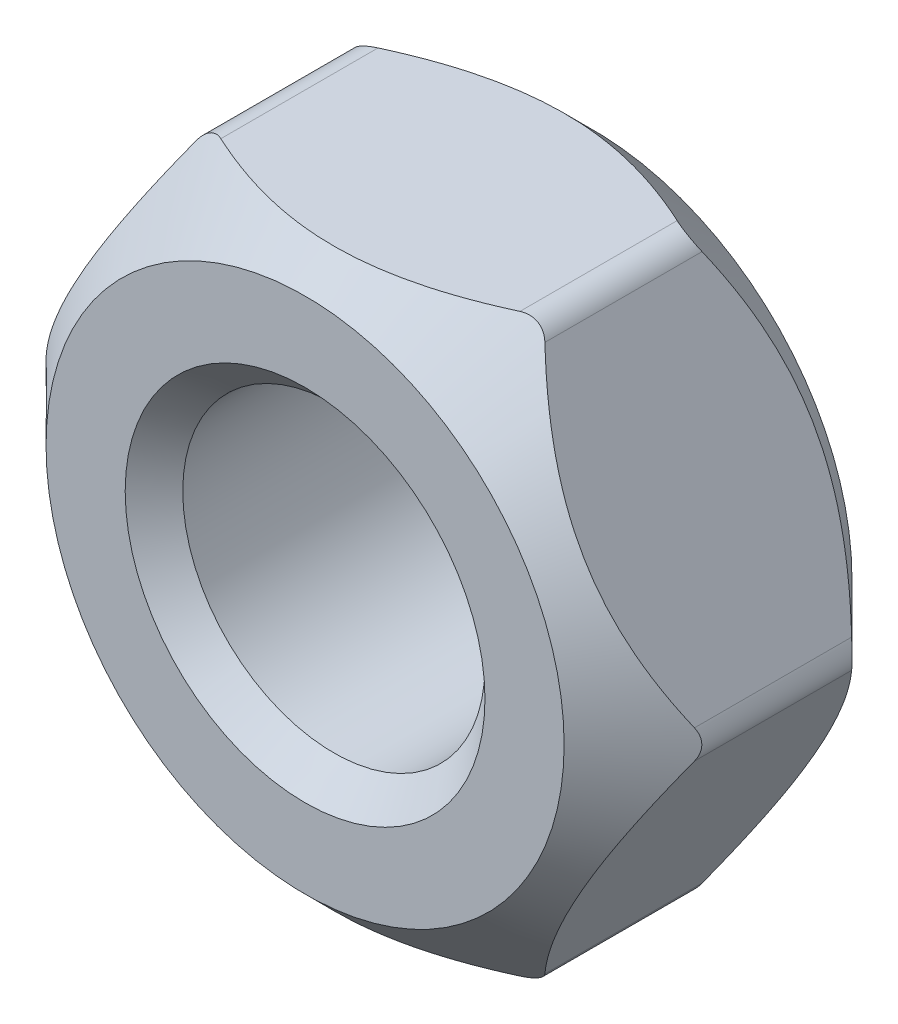
SolidWorks part; units mm, degrees
ref_plane "Front Plane" through (0, 0, 0) normal (0, 0, 1) x (1, 0, 0)
ref_plane "Top Plane" through (0, 0, 0) normal (0, 1, 0) x (1, 0, 0)
ref_plane "Right Plane" through (0, 0, 0) normal (1, 0, 0) x (0, 0, -1)
sketch "Sketch1" plane through (0, 0, 0) normal (0, 0, 1) x (1, 0, 0)
  line L1 (1.7321, 3) -> (-1.7321, 3)
  line L2 (-1.7321, 3) -> (-3.4641, 0)
  line L3 (-3.4641, 0) -> (-1.7321, -3)
  line L4 (-1.7321, -3) -> (1.7321, -3)
  line L5 (1.7321, -3) -> (3.4641, 0)
  line L6 (3.4641, 0) -> (1.7321, 3)
  circle A0 centre (0, 0) radius 1.575
  circle A1 centre (0, 0) radius 3 construction
  point P3 (2.103, 3.5722)
  dimension "D3" = 3.4641
  dimension "D1" = 3.15
  dimension "D2" = 6
extrude "Boss-Extrude1" add sketch "Sketch1" along normal mid plane 3
sketch "Sketch2" plane through (0, 0, 0) normal (1, 0, 0) x (0, 0, -1)
  line L0 (0, 0) -> (3.9985, 0) construction
  line L1 (1.5, 3.4641) -> (0.7359, 3.4641)
  line L3 (0.7359, 3.4641) -> (1.5, 2.7)
  line L4 (1.5, 0) -> (1.5, 3) construction
  line L5 (1.5, 2.7) -> (1.5, 3.4641)
  line L6 (-1.5, 3) -> (1.5, 3) construction
  point P6 (0.6782, 3.2303)
  point P7 (0, 0)
  point P8 (1.5, 3.1556)
  point P12 (0.6689, 3)
  dimension "D2" = 45
  dimension "D3" = 3.4641
  dimension "D1" = 0.3
revolve "Cut-Revolve1" cut sketch "Sketch2" angle 360 about L0
mirror "Mirror1" about plane through (0, 0, 0) normal (0, 0, 1) of "Cut-Revolve1"
fillet "Fillet1" radius 0.3 6 edges at (3.4641, 0, 0) (1.7321, -3, 0) (-1.7321, -3, 0) (-3.4641, 0, 0) (-1.7321, 3, 0) (1.7321, 3, 0)
chamfer "Chamfer1" distance 0.3 angle 45 2 edges at (1.575, 0, -1.5) (1.575, 0, 1.5)
sketch "STL Origin" plane through (0, 0, 1.5) normal (0, 0, 1) x (1, 0, 0)
  point P0 (0, 0)
equation "\"D3@Sketch2\"=\"D3@Sketch1\""
